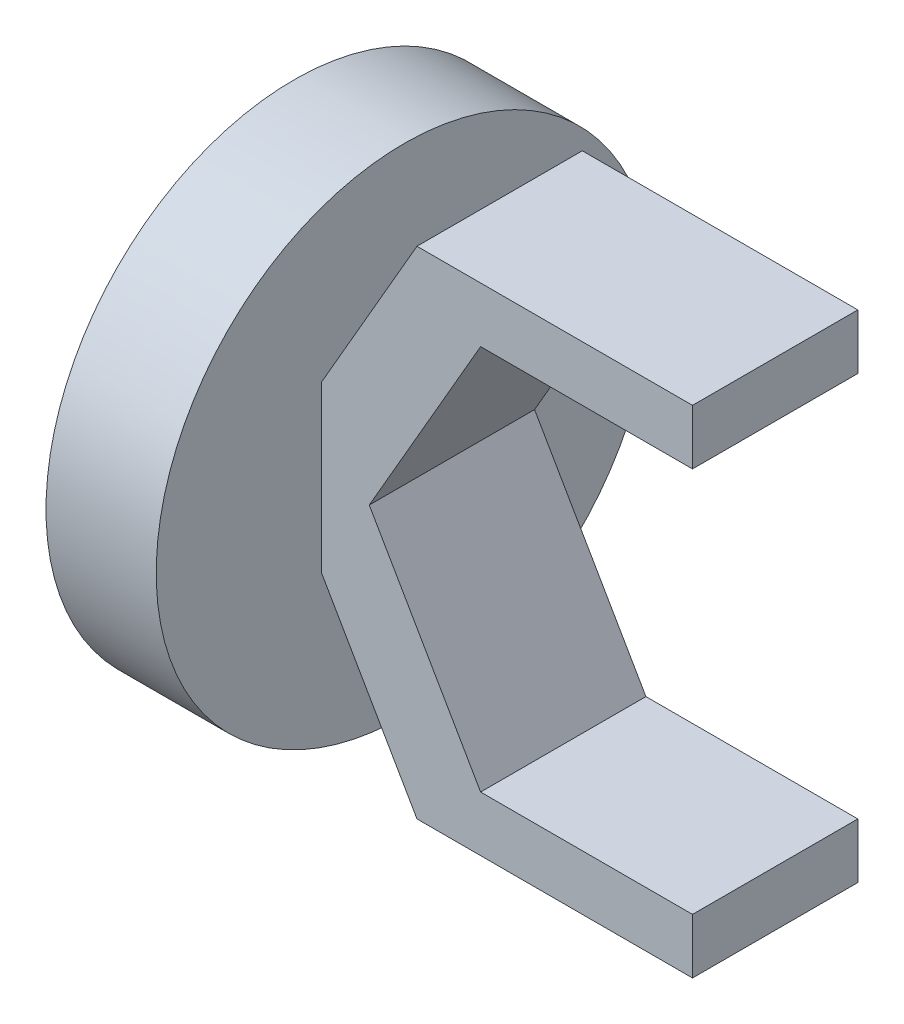
SolidWorks part; units mm, degrees
ref_plane "Front Plane" through (0, 0, 0) normal (0, 0, 1) x (1, 0, 0)
ref_plane "Top Plane" through (0, 0, 0) normal (0, 1, 0) x (1, 0, 0)
ref_plane "Right Plane" through (0, 0, 0) normal (1, 0, 0) x (0, 0, -1)
sketch "Sketch1" plane through (0, 0, 0) normal (1, 0, 0) x (0, 0, -1)
  circle A0 centre (0, 0) radius 45
  circle A1 centre (0, 0) radius 10
  dimension "D1" = 90
  dimension "D2" = 20
extrude "Boss-Extrude1" add sketch "Sketch1" along normal blind 20
sketch "Sketch2" plane through (20, 0, 0) normal (1, 0, 0) x (0, 0, -1)
  line L0 (0, -15) -> (0, 15) construction
  line L2 (12.5, -15) -> (-12.5, -15)
  line L3 (12.5, -15) -> (12.5, 15)
  line L4 (12.5, 15) -> (-12.5, 15)
  line L5 (-12.5, -15) -> (-12.5, 15)
  line L6 (12.5, -15) -> (-12.5, 15) construction
  line L7 (12.5, 15) -> (-12.5, -15) construction
  point P0 (0, 0)
  point P5 (0, 0)
  dimension "D1" = 30
  dimension "D2" = 25
  dimension "D3" = 30
sketch "Sketch3" plane through (0, 0, 0) normal (0, 0, 1) x (1, 0, 0)
  line L0 (20, 0) -> (46.0231, -45.0733) construction
  line L1 (20, -15) -> (20, 15) construction
  line L2 (20, -45) -> (70.3127, -45) construction
  line L3 (20, -15) -> (20, 15) construction
  line L4 (20, 0) -> (50020, 0) construction
  dimension "D1" = 30
sketch "Sketch4" plane through (0, 0, 0) normal (0, 0, 1) x (1, 0, 0)
  line L0 (0, 0) -> (50000, 0) construction
  line L1 (20, -15) -> (20, 15) construction
  line L2 (20, -45) -> (20, 45) construction
  line L3 (20, -15) -> (37.3205, -45)
  line L6 (20, 0) -> (46.0231, -45.0733) construction
  line L7 (20, -45) -> (70.3127, -45) construction
  line L8 (37.3205, -45) -> (87.3205, -45)
  line L9 (87.3205, -45) -> (87.3205, -35)
  line L10 (48.8675, -35) -> (28.6603, 0)
  line L11 (48.8675, -35) -> (87.3205, -35)
  line L12 (-199980, 0) -> (250020, 0) construction
  line L13 (0, 45) -> (0, -45) construction
  line L14 (48.8675, 35) -> (87.3205, 35)
  line L15 (48.8675, 35) -> (28.6603, 0)
  line L16 (87.3205, 45) -> (87.3205, 35)
  line L17 (37.3205, 45) -> (87.3205, 45)
  line L18 (20, 15) -> (37.3205, 45)
  line L19 (20, 15) -> (20, -15)
  point P23 (0, 0)
  dimension "D1" = 7.5
  dimension "D2" = 50
  dimension "D3" = 10
  dimension "D4" = 7.5
  dimension "D5" = 10
extrude "Boss-Extrude2" add sketch "Sketch4" along normal blind 15 and the other way blind 15
